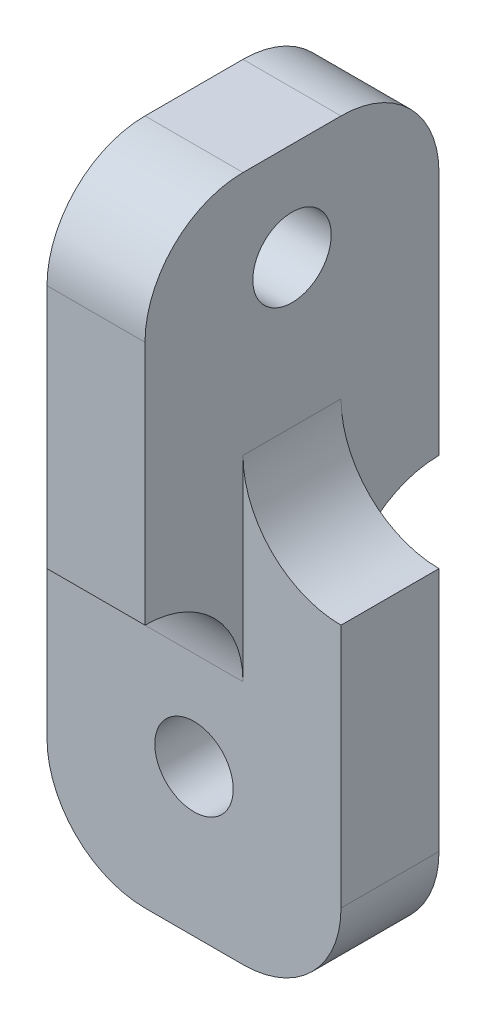
SolidWorks part; units mm, degrees
material "Stal nierdzewna (ferrytyczna)"
ref_plane "Front Plane" through (0, 0, 0) normal (0, 0, 1) x (1, 0, 0)
ref_plane "Top Plane" through (0, 0, 0) normal (0, 1, 0) x (1, 0, 0)
ref_plane "Right Plane" through (0, 0, 0) normal (1, 0, 0) x (0, 0, -1)
sketch "Sketch1" plane through (0, 0, 0) normal (0, 0, 1) x (1, 0, 0)
  line L1 (0, 0) -> (-30, 0)
  line L2 (0, 0) -> (0, -35)
  line L3 (0, -35) -> (-30, -35)
  line L4 (-30, 0) -> (-30, -35)
  dimension "D1" = 30
  dimension "D2" = 35
extrude "Boss-Extrude1" add sketch "Sketch1" along normal blind 10 contours L1 L4 L3 L2
fillet "Fillet1" radius 10 1 edges at (-30, -35, 5)
fillet "Fillet2" radius 10 1 edges at (0, -35, 5)
sketch "Sketch3" plane through (0, 0, 0) normal (0, 1, 0) x (1, 0, 0)
  line L0 (-30, -5) -> (0, -5) construction
  line L1 (-30, -10) -> (-30, 0) construction
  line L2 (0, -10) -> (0, 0) construction
sketch "Sketch5" plane through (0, 0, 10) normal (0, 0, 1) x (1, 0, 0)
sketch "Sketch11" plane through (0, 0, 0) normal (0, 0, 1) x (1, 0, 0)
  line L0 (-15, -35) -> (-15, -20) construction
  line L1 (-10, -35) -> (-20, -35) construction
  circle A0 centre (-15, -20) radius 4
  dimension "D1" = 8
extrude "Cut-Extrude3" cut sketch "Sketch11" along normal blind 14 contours A0
sketch "Sketch12" plane through (0, 0, 0) normal (0, 1, 0) x (1, 0, 0)
  line L0 (-30, -5) -> (0, -5) construction
  line L1 (-20, -20) -> (-10, -20)
  line L2 (-20, -20) -> (-20, 10)
  line L3 (-20, 10) -> (-10, 10)
  line L4 (-10, -20) -> (-10, 10)
  line L5 (-20, -20) -> (-10, 10) construction
  line L6 (-20, 10) -> (-10, -20) construction
  point P0 (-15, -5)
  dimension "D1" = 30
  dimension "D2" = 10
extrude "Boss-Extrude4" add sketch "Sketch12" along normal blind 35 contours L2 L3 L4 L1
sketch "Sketch13" plane through (0, 0, 0) normal (1, 0, 0) x (0, 0, -1)
sketch "Sketch15" plane through (-10, 0, 0) normal (1, 0, 0) x (0, 0, -1)
  line L0 (-5, 35) -> (-5, 25) construction
  line L1 (-20, 35) -> (10, 35) construction
  circle A0 centre (-5, 25) radius 4
  dimension "D1" = 8
extrude "Cut-Extrude4" cut sketch "Sketch15" against normal blind 35 contours A0
fillet "Fillet10" radius 10 1 edges at (-15, 35, -10)
fillet "Fillet11" radius 10 1 edges at (-15, 35, 20)
fillet "Fillet13" radius 10 1 edges at (-15, 0, 10)
fillet "Fillet14" radius 10 1 edges at (-15, 0, 0)
fillet "Fillet15" radius 10 1 edges at (-10, 0, 5)
fillet "Fillet16" radius 10 1 edges at (-20, 0, 5)
sketch "Szkic2" plane through (-20, 0, 0) normal (-1, 0, 0) x (0, 0, 1)
